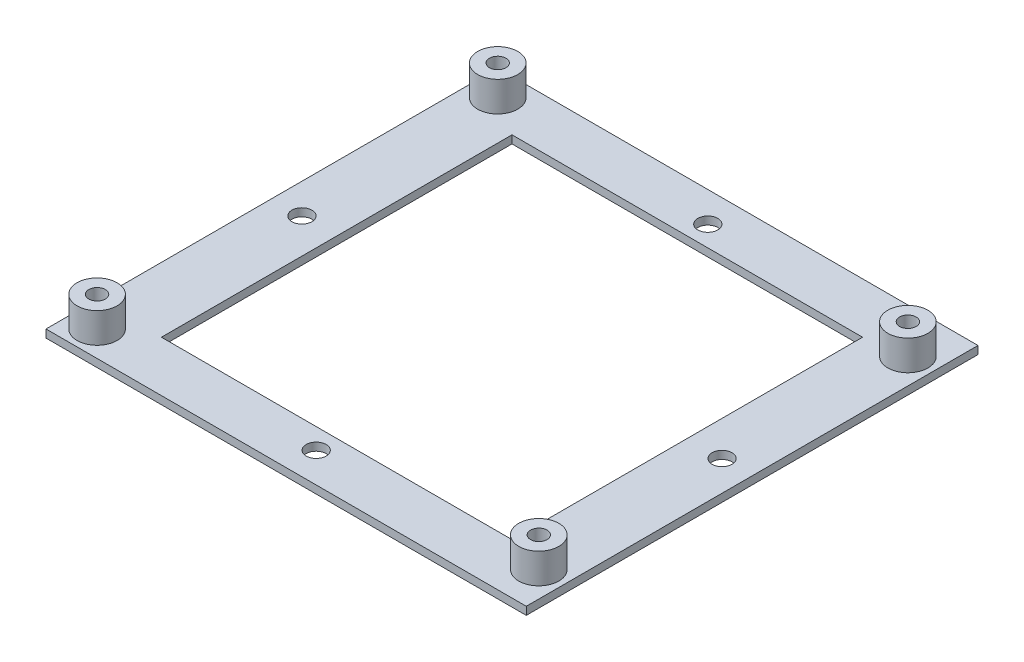
SolidWorks part; units mm, degrees
ref_plane "Front Plane" through (0, 0, 0) normal (0, 0, 1) x (1, 0, 0)
ref_plane "Top Plane" through (0, 0, 0) normal (0, 1, 0) x (1, 0, 0)
ref_plane "Right Plane" through (0, 0, 0) normal (1, 0, 0) x (0, 0, -1)
sketch "Sketch1" plane through (0, 0, 0) normal (0, 1, 0) x (1, 0, 0)
  line L1 (-47.95, -45.1) -> (47.95, -45.1)
  line L2 (-47.95, -45.1) -> (-47.95, 45.1)
  line L3 (-47.95, 45.1) -> (47.95, 45.1)
  line L4 (47.95, -45.1) -> (47.95, 45.1)
  line L5 (-47.95, -45.1) -> (47.95, 45.1) construction
  line L6 (-47.95, 45.1) -> (47.95, -45.1) construction
  circle A0 centre (-42.85, 40) radius 2
  circle A1 centre (42.85, 36.2) radius 2
  circle A2 centre (-42.85, -40) radius 2
  circle A3 centre (42.85, -37.5) radius 2
  point P0 (0, 0)
  point P6 (42.85, -37.5)
  point P7 (42.85, 36.2)
  point P8 (-42.85, 40)
  point P9 (-42.85, -40)
extrude "Boss-Extrude1" add sketch "Sketch1" along normal blind 1.58 contours L2 L1 L4 L3
sketch "Sketch2" plane through (0, 1.58, 0) normal (0, 1, 0) x (1, 0, 0)
  circle A0 centre (42.85, 36.2) radius 4
  circle A1 centre (42.85, -37.5) radius 4
  circle A2 centre (-42.85, -40) radius 4
  circle A3 centre (-42.85, 40) radius 4
  point P12 (0, 0)
extrude "Boss-Extrude2" add sketch "Sketch2" along normal blind 6
hole_wizard "M4x0.7 Tapped Hole1" positions "3DSketch1" profile "Sketch3" tap size "M4x0.7" standard "ANSI Metric"
sketch3d "3DSketch1"
  line L0 (-42.85, 7.58, -40) -> (-42.85, 1.58, -40) construction
  line L1 (-42.85, 7.58, 40) -> (-42.85, 1.58, 40) construction
  line L2 (42.85, 7.58, 37.5) -> (42.85, 1.58, 37.5) construction
  line L3 (42.85, 7.58, -36.2) -> (42.85, 1.58, -36.2) construction
  point P0 (-42.85, 7.58, -40)
  point P4 (-42.85, 7.58, 40)
  point P8 (42.85, 7.58, 37.5)
  point P12 (42.85, 7.58, -36.2)
sketch "Sketch3" plane through (-42.85, 7.58, -40) normal (1, 0, 0) x (0, 0, 1)
  line L0 (0, 0) -> (0, 6.9914)
  line L1 (0, 6.9914) -> (1.65, 6)
  line L2 (1.65, 6) -> (1.65, 0)
  line L5 (1.65, 0) -> (0, 0)
  line L10 (0, 6.9914) -> (-1.65, 6) construction
  line L11 (0, -6.35) -> (0, 107.95) construction
  dimension "Tap Drill Dia." = 3.3
  dimension "Tap Drill Depth" = 6
  dimension "Drill Angle" = 118
cosmetic thread "Hole Thread1" parameters "D1"=6, "D2"=4
cosmetic thread "Hole Thread2" parameters "D1"=6, "D2"=4
cosmetic thread "Hole Thread3" parameters "D1"=6, "D2"=4
cosmetic thread "Hole Thread4" parameters "D1"=6, "D2"=4
sketch "Sketch4" plane through (0, 1.58, 0) normal (0, 1, 0) x (1, 0, 0)
  line L0 (-3017.5185, 45.1) -> (46982.4815, 45.1) construction
  line L1 (-47.95, 0) -> (-41.95, 0) construction
  line L2 (-998.6049, -45.1) -> (49001.3951, -45.1) construction
  line L3 (47.95, 0) -> (41.95, 0) construction
  line L4 (-47.95, -2995.2812) -> (-47.95, 47004.7188) construction
  line L5 (0, 45.1) -> (0, 39.1) construction
  line L6 (47.95, -1002.9584) -> (47.95, 48997.0416) construction
  line L7 (0, -45.1) -> (0, -39.1) construction
  line L8 (0, -3000) -> (0, 3000) construction
  line L9 (-3000, 0) -> (3000, 0) construction
  line L10 (47.95, -45.1) -> (47.95, 45.1) construction
  line L11 (-47.95, -45.1) -> (47.95, -45.1) construction
  line L12 (-47.95, -45.1) -> (-47.95, 45.1) construction
  line L13 (-47.95, 45.1) -> (47.95, 45.1) construction
  line L15 (-35, -35) -> (35, -35)
  line L16 (-35, -35) -> (-35, 35)
  line L17 (-35, 35) -> (35, 35)
  line L18 (35, -35) -> (35, 35)
  line L19 (-35, -35) -> (35, 35) construction
  line L20 (-35, 35) -> (35, -35) construction
  circle A0 centre (0, 39.1) radius 2
  circle A1 centre (41.95, 0) radius 2
  circle A2 centre (0, -39.1) radius 2
  circle A3 centre (-41.95, 0) radius 2
  point P4 (21982.4815, 45.1)
  point P6 (47.95, 0)
  point P9 (-47.95, 22004.7188)
  point P11 (0, -45.1)
  point P15 (0, 0)
  point P18 (0, 0)
  point P21 (-47.95, 0)
  point P24 (0, 45.1)
  point P41 (35, 35)
  point P42 (0, 0)
extrude "Cut-Extrude1" cut sketch "Sketch4" against normal through all both and the other way through all
